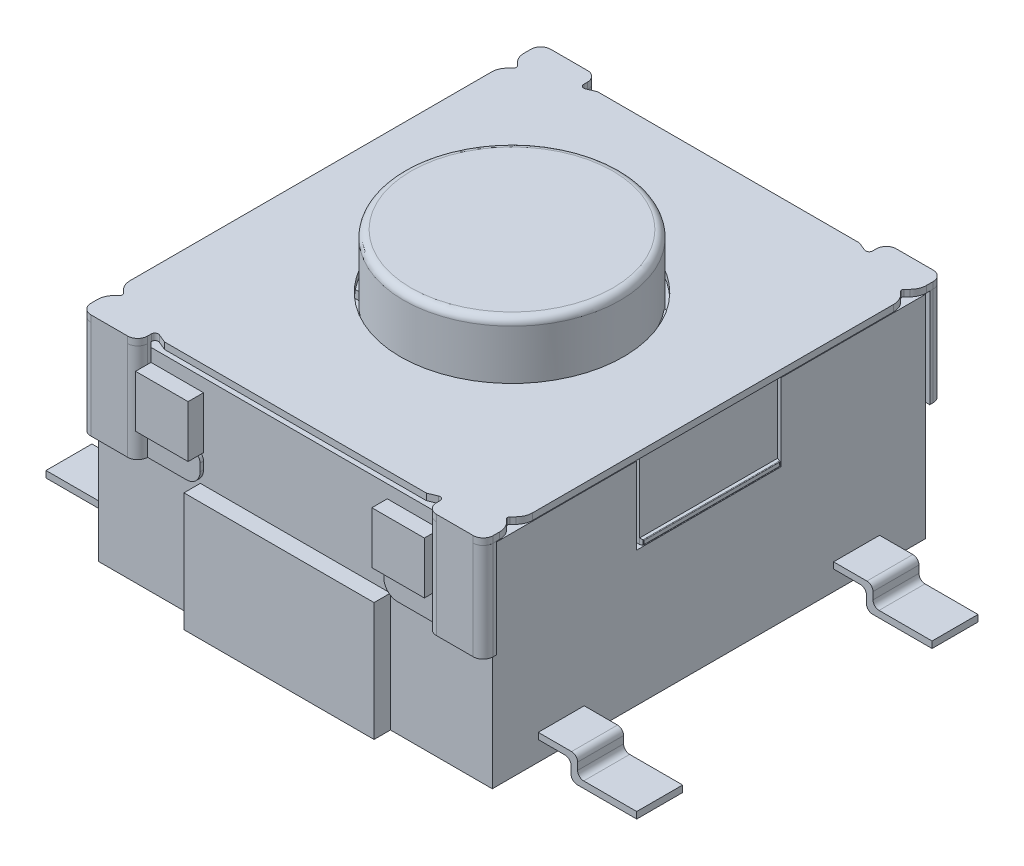
SolidWorks part; units mm, degrees
ref_plane "Alzado" through (0, 0, 0) normal (0, 0, 1) x (1, 0, 0)
ref_plane "Planta" through (0, 0, 0) normal (0, 1, 0) x (1, 0, 0)
ref_plane "Vista lateral" through (0, 0, 0) normal (1, 0, 0) x (0, 0, -1)
sketch "Croquis1" plane through (0, 0, 0) normal (0, 0, 1) x (1, 0, 0)
  line L0 (0, 0) -> (9, 0) construction
  line L1 (4.5, 0) -> (4.5, 3.4) construction
  line L2 (4.5, 1.7) -> (7.5, 1.7) construction
  line L3 (4.5, 1.7) -> (1.5, 1.7) construction
  line L4 (1.5, 1.7) -> (1.5, 0) construction
  line L5 (7.5, 1.7) -> (7.5, 0) construction
  line L6 (1.5, 0.85) -> (1, 0.85) construction
  line L7 (7.5, 0.85) -> (8, 0.85) construction
  line L8 (0, 0) -> (0, 0.1) construction
  line L9 (0, 0) -> (0.9075, 0)
  line L10 (1, 0.0925) -> (1, 0.2069)
  line L11 (1.0925, 0.2994) -> (7.9075, 0.2994)
  line L13 (0, 0.1) -> (0, 0)
  line L14 (1, 0.2994) -> (0.9, 0.2994) construction
  line L15 (0.9, 0.2994) -> (0.9, 0.1925)
  line L16 (0.8075, 0.1) -> (0, 0.1)
  line L17 (8.0075, 0.3946) -> (0.9925, 0.3946)
  line L18 (0.9, 0.3021) -> (0.9, 0.2994)
  line L19 (8, 0.2994) -> (8.1, 0.2994) construction
  line L20 (9, 0) -> (9, 0.1) construction
  line L21 (7.5, 0.85) -> (8, 0.85) construction
  line L22 (8.1, 0.3021) -> (8.1, 0.2994)
  line L23 (8.1925, 0.1) -> (9, 0.1)
  line L24 (8.1, 0.2994) -> (8.1, 0.1925)
  line L25 (9, 0.1) -> (9, 0)
  line L26 (8, 0.0925) -> (8, 0.2069)
  line L27 (9, 0) -> (8.0925, 0)
  arc A0 (0.9, 0.3021) -> (0.9925, 0.3946) centre (0.9925, 0.3021) cw
  arc A1 (1, 0.2069) -> (1.0925, 0.2994) centre (1.0925, 0.2069) cw
  arc A2 (0.8075, 0.1) -> (0.9, 0.1925) centre (0.8075, 0.1925) ccw
  arc A3 (0.9075, 0) -> (1, 0.0925) centre (0.9075, 0.0925) ccw
  arc A4 (8.0925, 0) -> (8, 0.0925) centre (8.0925, 0.0925) cw
  arc A5 (8.1925, 0.1) -> (8.1, 0.1925) centre (8.1925, 0.1925) cw
  arc A6 (8, 0.2069) -> (7.9075, 0.2994) centre (7.9075, 0.2069) ccw
  arc A7 (8.1, 0.3021) -> (8.0075, 0.3946) centre (8.0075, 0.3021) ccw
  point P31 (1, 0)
  point P47 (8, 0)
  dimension "D9" = 0.0925
  dimension "D1" = 9
  dimension "D2" = 3
  dimension "D3" = 3
  dimension "D4" = 0.5
  dimension "D5" = 0.5
  dimension "D6" = 0.1
  dimension "D7" = 3.4
  dimension "D8" = 0.1
extrude "Saliente-Extruir1" add sketch "Croquis1" along normal blind 5.2
sketch "Croquis2" plane through (0, 0.3946, 0) normal (0, 1, 0) x (1, 0, 0)
  line L0 (4.5, 0) -> (4.5, -5.2) construction
  line L1 (8.0075, 0) -> (0.9925, 0) construction
  line L2 (8.0075, -5.2) -> (0.9925, -5.2) construction
  line L3 (0.9925, -2.6) -> (8.0075, -2.6) construction
  line L4 (0.9925, -5.2) -> (0.9925, 0) construction
  line L5 (8.0075, -5.2) -> (8.0075, 0) construction
  line L6 (9, -5.2) -> (9, 0) construction
  line L7 (0, -0.7) -> (9, -0.7)
  line L8 (0, -0.7) -> (0, -4.5)
  line L9 (0, -4.5) -> (9, -4.5)
  line L10 (9, -0.7) -> (9, -4.5)
  line L11 (0, -0.7) -> (9, -4.5) construction
  line L12 (0, -4.5) -> (9, -0.7) construction
  point P12 (4.5, -2.6)
  dimension "D1" = 3.8
extrude "Cortar-Extruir1" cut sketch "Croquis2" against normal blind 5.2
sketch "Croquis3" plane through (0, 0.2994, 0) normal (0, -1, 0) x (1, 0, 0)
  line L0 (4.5, 0.7) -> (4.5, 4.5) construction
  line L1 (7.9075, 0.7) -> (1.0925, 0.7) construction
  line L2 (1.0925, 4.5) -> (7.9075, 4.5) construction
  line L3 (3.7616, 2.6) -> (5.3308, 2.6) construction
  line L5 (7.5, -0.7) -> (1.5, -0.7)
  line L6 (7.5, -0.7) -> (7.5, 5.9)
  line L7 (7.5, 5.9) -> (1.5, 5.9)
  line L8 (1.5, -0.7) -> (1.5, 5.9)
  line L9 (7.5, -0.7) -> (1.5, 5.9) construction
  line L10 (7.5, 5.9) -> (1.5, -0.7) construction
  point P8 (4.5, 2.6)
  dimension "D1" = 6.6
  dimension "D2" = 6
extrude "Saliente-Extruir2" add sketch "Croquis3" along normal blind 0.3 and the other way blind 3
sketch "Croquis4" plane through (0, 3.2994, 0) normal (0, 1, 0) x (1, 0, 0)
  line L0 (4.5, 0.7) -> (4.5, -5.9) construction
  line L1 (1.5, 0.7) -> (7.5, 0.7) construction
  line L2 (7.5, -5.9) -> (1.5, -5.9) construction
  line L3 (4.5, -5.9) -> (1.5, -2.6) construction
  line L4 (1.5, -5.9) -> (1.5, 0.7) construction
  line L5 (1.5, -2.6) -> (7.5, -2.6) construction
  line L6 (7.5, 0.7) -> (7.5, -5.9) construction
  circle A0 centre (4.5, -2.6) radius 1.65
  dimension "D1" = 3.3
extrude "Cortar-Extruir2" cut sketch "Croquis4" against normal blind 1.3
sketch "Croquis5" plane through (0, 3.2994, 0) normal (0, 1, 0) x (1, 0, 0)
  line L0 (1.5, -5.9) -> (1.5, -6.3533) construction
  line L1 (1.5, -6.3533) -> (2.3, -6.3533) construction
  line L2 (4.5, -5.9) -> (4.5, -4.25) construction
  line L3 (7.5, -5.9) -> (1.5, -5.9) construction
  line L5 (2.5047, -5.9) -> (2.3734, -5.8453)
  line L6 (2.3, -5.8943) -> (2.3, -5.951)
  line L7 (2.1477, -6.1033) -> (1.5874, -6.1033)
  line L8 (1.4351, -5.951) -> (1.4351, -5.8529)
  line L9 (1.5097, -5.6729) -> (1.5536, -5.629)
  line L10 (1.581, -5.6016) -> (1.3352, -5.6016) construction
  line L11 (1.5097, -5.5303) -> (1.5536, -5.5742)
  line L12 (1.4351, -5.3503) -> (1.4351, -3.1032)
  line L14 (7.419, -5.6016) -> (7.6648, -5.6016) construction
  line L15 (7.5, -6.3533) -> (6.7, -6.3533) construction
  line L16 (7.5, -5.9) -> (7.5, -6.3533) construction
  line L17 (7.5649, -5.3503) -> (7.5649, -3.1032)
  line L18 (7.4903, -5.5303) -> (7.4464, -5.5742)
  line L19 (7.4903, -5.6729) -> (7.4464, -5.629)
  line L20 (7.5649, -5.951) -> (7.5649, -5.8529)
  line L21 (6.8523, -6.1033) -> (7.4126, -6.1033)
  line L22 (6.7, -5.8943) -> (6.7, -5.951)
  line L23 (6.4953, -5.9) -> (6.6266, -5.8453)
  line L24 (4.5, -2.6) -> (0.57, -2.6) construction
  line L25 (7.5, 0.7) -> (7.5, 1.1533) construction
  line L26 (7.5, 1.1533) -> (6.7, 1.1533) construction
  line L27 (7.419, 0.4016) -> (7.6648, 0.4016) construction
  line L28 (1.581, 0.4016) -> (1.3352, 0.4016) construction
  line L29 (4.5, 0.7) -> (4.5, -0.95) construction
  line L30 (1.5, 1.1533) -> (2.3, 1.1533) construction
  line L31 (1.5, 0.7) -> (1.5, 1.1533) construction
  line L32 (6.4953, 0.7) -> (6.6266, 0.6453)
  line L33 (6.7, 0.6943) -> (6.7, 0.751)
  line L34 (6.8523, 0.9033) -> (7.4126, 0.9033)
  line L35 (7.5649, 0.751) -> (7.5649, 0.6529)
  line L36 (7.4903, 0.4729) -> (7.4464, 0.429)
  line L37 (7.4903, 0.3303) -> (7.4464, 0.3742)
  line L38 (7.5649, 0.1503) -> (7.5649, -2.0968)
  line L40 (1.4351, 0.1503) -> (1.4351, -2.0968)
  line L41 (1.5097, 0.3303) -> (1.5536, 0.3742)
  line L42 (1.5097, 0.4729) -> (1.5536, 0.429)
  line L43 (1.4351, 0.751) -> (1.4351, 0.6529)
  line L44 (2.1477, 0.9033) -> (1.5874, 0.9033)
  line L45 (2.3, 0.6943) -> (2.3, 0.751)
  line L46 (2.5047, 0.7) -> (2.3734, 0.6453)
  line L48 (2.5047, 0.7) -> (6.4953, 0.7)
  line L49 (7.5649, -2.0968) -> (7.5649, -3.1032)
  line L50 (6.4953, -5.9) -> (2.5047, -5.9)
  line L51 (1.4351, -3.1032) -> (1.4351, -2.0968)
  circle A0 centre (4.5, -2.6) radius 1.65 construction
  arc A1 (1.5536, -5.629) -> (1.5536, -5.5742) centre (1.5262, -5.6016) ccw
  arc A2 (1.4351, -5.8529) -> (1.5097, -5.6729) centre (1.6897, -5.8529) cw
  arc A3 (1.5097, -5.5303) -> (1.4351, -5.3503) centre (1.6897, -5.3503) cw
  arc A4 (2.3, -5.951) -> (2.1477, -6.1033) centre (2.1477, -5.951) cw
  arc A5 (1.4351, -5.951) -> (1.5874, -6.1033) centre (1.5874, -5.951) ccw
  arc A6 (2.3734, -5.8453) -> (2.3, -5.8943) centre (2.353, -5.8943) ccw
  arc A7 (6.6266, -5.8453) -> (6.7, -5.8943) centre (6.647, -5.8943) cw
  arc A8 (7.5649, -5.951) -> (7.4126, -6.1033) centre (7.4126, -5.951) cw
  arc A9 (6.7, -5.951) -> (6.8523, -6.1033) centre (6.8523, -5.951) ccw
  arc A10 (7.4903, -5.5303) -> (7.5649, -5.3503) centre (7.3103, -5.3503) ccw
  arc A11 (7.5649, -5.8529) -> (7.4903, -5.6729) centre (7.3103, -5.8529) ccw
  arc A12 (7.4464, -5.629) -> (7.4464, -5.5742) centre (7.4738, -5.6016) cw
  arc A13 (7.4464, 0.429) -> (7.4464, 0.3742) centre (7.4738, 0.4016) ccw
  arc A14 (7.5649, 0.6529) -> (7.4903, 0.4729) centre (7.3103, 0.6529) cw
  arc A15 (7.4903, 0.3303) -> (7.5649, 0.1503) centre (7.3103, 0.1503) cw
  arc A16 (6.7, 0.751) -> (6.8523, 0.9033) centre (6.8523, 0.751) cw
  arc A17 (7.5649, 0.751) -> (7.4126, 0.9033) centre (7.4126, 0.751) ccw
  arc A18 (6.6266, 0.6453) -> (6.7, 0.6943) centre (6.647, 0.6943) ccw
  arc A19 (2.3734, 0.6453) -> (2.3, 0.6943) centre (2.353, 0.6943) cw
  arc A20 (1.4351, 0.751) -> (1.5874, 0.9033) centre (1.5874, 0.751) cw
  arc A21 (2.3, 0.751) -> (2.1477, 0.9033) centre (2.1477, 0.751) ccw
  arc A22 (1.5097, 0.3303) -> (1.4351, 0.1503) centre (1.6897, 0.1503) ccw
  arc A23 (1.4351, 0.6529) -> (1.5097, 0.4729) centre (1.6897, 0.6529) ccw
  arc A24 (1.5536, 0.429) -> (1.5536, 0.3742) centre (1.5262, 0.4016) cw
  point P26 (1.4351, -5.7475)
  point P29 (1.4351, -5.4558)
  point P61 (7.5649, -5.4558)
  point P62 (7.5649, -5.7475)
  point P118 (7.5649, 0.5475)
  point P119 (7.5649, 0.2558)
  point P120 (1.4351, 0.2558)
  point P121 (1.4351, 0.5475)
  dimension "D2" = 0.0387
  dimension "D3" = 0.2546
  dimension "D4" = 0.1523
  dimension "D5" = 0.053
  dimension "D1" = 0.8
extrude "Saliente-Extruir3" add sketch "Croquis5" along normal blind 0.1
sketch "Croquis6" plane through (0, 3.3994, 0) normal (0, 1, 0) x (1, 0, 0)
  line L0 (4.5, 0.7) -> (4.5, -5.9) construction
  line L1 (6.4953, 0.7) -> (2.5047, 0.7) construction
  line L2 (2.5047, -5.9) -> (6.4953, -5.9) construction
  line L3 (4.5, -5.9) -> (1.4351, -2.6) construction
  line L4 (1.4351, 0.1503) -> (1.4351, -5.3503) construction
  line L5 (1.4351, -2.6) -> (4.5, -2.6) construction
  circle A0 centre (4.5, -2.6) radius 1.7
  dimension "D1" = 3.4
extrude "Cortar-Extruir3" cut sketch "Croquis6" against normal blind 0.1
sketch "Croquis7" plane through (7.5, 0, 0) normal (1, 0, 0) x (0, 0, -1)
  line L0 (-2.6, 3.2994) -> (-2.6, 1.1616) construction
  line L1 (-5.3503, 3.2994) -> (0.1503, 3.2994) construction
  line L2 (-2.6, 1.1616) -> (-1.5, 1.1616) construction
  line L3 (-2.6, 1.1616) -> (-3.7, 1.1616) construction
  line L4 (-3.7, 1.1616) -> (-3.7, 3.2994) construction
  line L5 (-3.7, 3.2994) -> (-1.5, 1.1616) construction
  line L6 (-1.5, 1.1616) -> (-1.5, 3.2994) construction
  line L7 (0.3201, 3.2994) -> (-5.5201, 3.2994) construction
  line L8 (-5.2012, 3.2994) -> (-5.2012, 2.0494) construction
  line L9 (-5.2012, 2.0494) -> (0.7, 2.0494) construction
  line L10 (0.7, 3.2994) -> (0.7, -0.0006) construction
  line L11 (-5.9, 3.2994) -> (-3.6554, 3.2994)
  line L12 (0.7, 3.2242) -> (0.7, 3.2994)
  line L13 (0.7, 3.2242) -> (-1.5, 3.2242)
  line L14 (-1.5, 3.2242) -> (-1.5, 2.0494)
  line L15 (-1.5, 2.0494) -> (-3.7, 2.0494)
  line L16 (-3.7, 2.0494) -> (-3.7, 3.2242)
  line L17 (-3.7, 3.2242) -> (-5.9, 3.2242)
  line L18 (-5.9, 3.2994) -> (-5.9, -0.0006) construction
  line L19 (-5.9, 3.2242) -> (-5.9, 3.2994)
  line L21 (-3.6554, 3.2994) -> (-3.6554, 2.1002)
  line L22 (-3.6554, 2.1002) -> (-1.5557, 2.1002)
  line L23 (-1.5557, 2.1002) -> (-1.5557, 3.2994)
  line L24 (-1.5557, 3.2994) -> (0.7, 3.2994)
  dimension "D1" = 1.1
  dimension "D2" = 1.1
  dimension "D3" = 1.25
extrude "Cortar-Extruir4" cut sketch "Croquis7" against normal blind 7.1
sketch "Croquis9" plane through (7.5, 0, 0) normal (1, 0, 0) x (0, 0, -1)
  line L0 (-3.6554, 2.1002) -> (-3.6554, 3.2994) construction
  line L1 (-1.5557, 2.1002) -> (-3.6554, 2.1002)
  line L2 (-1.5557, 2.1002) -> (-1.5557, 2.1873)
  line L3 (-1.5557, 2.1873) -> (-3.6554, 2.1873)
  line L4 (-3.6554, 2.1002) -> (-3.6554, 2.1873)
extrude "Saliente-Extruir4" add sketch "Croquis9" along normal blind 0.05 draft 10
fillet "Redondeo1" radius 0.01 4 edges at (7.55, 2.109, 2.6055) (7.55, 2.1437, 3.6466) (7.55, 2.1785, 2.6055) (7.55, 2.1437, 1.5645)
sketch "Croquis10" plane through (1.5, 0, 0) normal (-1, 0, 0) x (0, 0, 1)
  line L0 (1.5557, 2.1002) -> (1.5557, 3.2994) construction
  line L1 (3.6554, 2.1002) -> (1.5557, 2.1002)
  line L2 (3.6554, 2.1002) -> (3.6554, 2.2063)
  line L3 (3.6554, 2.2063) -> (1.5557, 2.2063)
  line L4 (1.5557, 2.1002) -> (1.5557, 2.2063)
extrude "Saliente-Extruir5" add sketch "Croquis10" along normal blind 0.05 draft 10
fillet "Redondeo2" radius 0.01 4 edges at (1.45, 2.109, 2.6055) (1.45, 2.1532, 1.5645) (1.45, 2.1975, 2.6055) (1.45, 2.1532, 3.6466)
sketch "Croquis11" plane through (0, 3.2994, 0) normal (0, -1, 0) x (1, 0, 0)
  line L2 (2.1477, 6.1033) -> (2.3213, 6.1033) construction
  line L3 (2.3, 5.9) -> (2.3, 5.9512)
  line L4 (2.3, 5.951) -> (2.3, 5.8943) construction
  line L5 (7.5, 5.9) -> (1.5, 5.9) construction
  line L6 (2.1478, 6.1033) -> (2.1477, 6.1033)
  line L7 (1.5, 5.9) -> (1.3098, 5.9) construction
  line L8 (1.5, 5.9) -> (1.5, -0.7) construction
  line L9 (1.5874, 6.1033) -> (1.2856, 6.1033) construction
  line L10 (1.4346, 5.9) -> (1.4351, 5.9526)
  line L11 (1.5872, 6.1033) -> (1.5874, 6.1033)
  line L12 (1.5874, 6.1033) -> (2.1477, 6.1033)
  line L13 (1.4346, 5.9) -> (2.3, 5.9)
  line L14 (4.5, 5.9) -> (4.5, -0.7) construction
  line L15 (1.5, -0.7) -> (7.5, -0.7) construction
  line L16 (4.5, 2.6) -> (1.5, 2.6) construction
  line L17 (7.4126, 6.1033) -> (7.7144, 6.1033) construction
  line L18 (7.5, 5.9) -> (7.6902, 5.9) construction
  line L19 (6.8523, 6.1033) -> (6.6787, 6.1033) construction
  line L20 (7.5654, 5.9) -> (6.7, 5.9)
  line L21 (7.4126, 6.1033) -> (6.8523, 6.1033)
  line L22 (7.4128, 6.1033) -> (7.4126, 6.1033)
  line L23 (7.5654, 5.9) -> (7.5649, 5.9526)
  line L24 (6.8522, 6.1033) -> (6.8523, 6.1033)
  line L25 (6.7, 5.9) -> (6.7, 5.9512)
  line L26 (6.8523, -0.9033) -> (6.6787, -0.9033) construction
  line L27 (7.5, -0.7) -> (7.6902, -0.7) construction
  line L28 (7.4126, -0.9033) -> (7.7144, -0.9033) construction
  line L29 (1.5874, -0.9033) -> (1.2856, -0.9033) construction
  line L30 (1.5, -0.7) -> (1.3098, -0.7) construction
  line L31 (2.1477, -0.9033) -> (2.3213, -0.9033) construction
  line L32 (6.7, -0.7) -> (6.7, -0.7512)
  line L33 (6.8522, -0.9033) -> (6.8523, -0.9033)
  line L34 (7.5654, -0.7) -> (7.5649, -0.7526)
  line L35 (7.4128, -0.9033) -> (7.4126, -0.9033)
  line L36 (7.4126, -0.9033) -> (6.8523, -0.9033)
  line L37 (7.5654, -0.7) -> (6.7, -0.7)
  line L38 (1.4346, -0.7) -> (2.3, -0.7)
  line L39 (1.5874, -0.9033) -> (2.1477, -0.9033)
  line L40 (1.5872, -0.9033) -> (1.5874, -0.9033)
  line L41 (1.4346, -0.7) -> (1.4351, -0.7526)
  line L42 (2.1478, -0.9033) -> (2.1477, -0.9033)
  line L43 (2.3, -0.7) -> (2.3, -0.7512)
  arc A1 (2.3, 5.9512) -> (2.1478, 6.1033) centre (2.1478, 5.9512) ccw
  arc A2 (1.4351, 5.9526) -> (1.5872, 6.1033) centre (1.5872, 5.9512) cw
  arc A3 (7.5649, 5.9526) -> (7.4128, 6.1033) centre (7.4128, 5.9512) ccw
  arc A4 (6.7, 5.9512) -> (6.8522, 6.1033) centre (6.8522, 5.9512) cw
  arc A5 (6.7, -0.7512) -> (6.8522, -0.9033) centre (6.8522, -0.7512) ccw
  arc A6 (7.5649, -0.7526) -> (7.4128, -0.9033) centre (7.4128, -0.7512) cw
  arc A7 (1.4351, -0.7526) -> (1.5872, -0.9033) centre (1.5872, -0.7512) ccw
  arc A8 (2.3, -0.7512) -> (2.1478, -0.9033) centre (2.1478, -0.7512) cw
  point P10 (2.3, 6.1033)
  point P23 (1.4365, 6.1033)
  point P44 (7.5635, 6.1033)
  point P45 (6.7, 6.1033)
  point P74 (6.7, -0.9033)
  point P75 (7.5635, -0.9033)
  point P76 (1.4365, -0.9033)
  point P77 (2.3, -0.9033)
  dimension "D1" = 0.1522
  dimension "D2" = 0.1522
extrude "Saliente-Extruir6" add sketch "Croquis11" along normal blind 1.5
sketch "Croquis12" plane through (2.3, 0, 0) normal (1, 0, 0) x (0, 0, -1)
  line L0 (-5.9526, 1.7994) -> (-5.9526, 3.2994) construction
  line L1 (-5.9, 1.7994) -> (-5.9526, 1.7994)
  line L2 (-5.9, 1.7994) -> (-5.9, 2.2341)
  line L3 (-5.9, 2.2341) -> (-5.9526, 2.2341)
  line L4 (-5.9526, 1.7994) -> (-5.9526, 2.2341)
extrude "Saliente-Extruir7" add sketch "Croquis12" along normal blind 0.8
fillet "Redondeo4" radius 0.21 1 edges at (3.1, 1.7994, 5.9263)
fillet "Redondeo5" radius 0.11 1 edges at (3.1, 2.2341, 5.9263)
sketch "Croquis13" plane through (6.7, 0, 0) normal (-1, 0, 0) x (0, 0, 1)
  line L0 (5.9, 3.2242) -> (5.9, 1.7994) construction
  line L1 (5.9526, 1.7994) -> (5.9, 1.7994)
  line L2 (5.9526, 1.7994) -> (5.9526, 2.2282)
  line L3 (5.9526, 2.2282) -> (5.9, 2.2282)
  line L4 (5.9, 1.7994) -> (5.9, 2.2282)
extrude "Saliente-Extruir8" add sketch "Croquis13" along normal blind 0.8
fillet "Redondeo6" radius 0.21 1 edges at (5.9, 1.7994, 5.9263)
fillet "Redondeo7" radius 0.11 1 edges at (5.9, 2.2282, 5.9263)
sketch "Croquis14" plane through (6.7, 0, 0) normal (-1, 0, 0) x (0, 0, 1)
  line L0 (-0.7526, 1.7994) -> (-0.7526, 3.2994) construction
  line L1 (-0.7, 1.7994) -> (-0.7526, 1.7994)
  line L2 (-0.7, 1.7994) -> (-0.7, 2.2283)
  line L3 (-0.7, 2.2283) -> (-0.7526, 2.2283)
  line L4 (-0.7526, 1.7994) -> (-0.7526, 2.2283)
extrude "Saliente-Extruir9" add sketch "Croquis14" along normal blind 0.8
fillet "Redondeo8" radius 0.21 1 edges at (5.9, 1.7994, -0.7263)
fillet "Redondeo9" radius 0.11 1 edges at (5.9, 2.2283, -0.7263)
sketch "Croquis15" plane through (2.3, 0, 0) normal (1, 0, 0) x (0, 0, -1)
  line L0 (0.7, 3.2242) -> (0.7, 1.7994) construction
  line L1 (0.7512, 1.7994) -> (0.7, 1.7994)
  line L2 (0.7512, 1.7994) -> (0.7512, 2.2355)
  line L3 (0.7512, 2.2355) -> (0.7, 2.2355)
  line L4 (0.7, 1.7994) -> (0.7, 2.2355)
extrude "Saliente-Extruir10" add sketch "Croquis15" along normal blind 0.8
fillet "Redondeo10" radius 0.11 1 edges at (3.1, 2.2355, -0.7256)
fillet "Redondeo11" radius 0.21 1 edges at (3.1, 1.7994, -0.7256)
sketch "Croquis16" plane through (0, 0, -0.7) normal (0, 0, -1) x (-1, 0, 0)
  line L0 (-6.7, 2.2348) -> (-5.6092, 2.2348) construction
  line L1 (-6.7, 2.2283) -> (-6.7, 3.2242) construction
  line L2 (-5.9, 2.0094) -> (-5.9, 2.5471) construction
  line L3 (-4.5, 3.2242) -> (-4.5, 2.0094) construction
  line L4 (-5.9, 2.2348) -> (-6.7, 2.2348)
  line L5 (-5.9, 2.2348) -> (-5.9, 3.0259)
  line L6 (-5.9, 3.0259) -> (-6.7, 3.0259)
  line L7 (-6.7, 2.2348) -> (-6.7, 3.0259)
  line L8 (-2.3, 3.2242) -> (-6.7, 3.2242) construction
  line L9 (-3.1, 2.0094) -> (-3.1, 2.5471) construction
  line L10 (-2.3, 2.2348) -> (-3.3908, 2.2348) construction
  line L11 (-2.3, 2.2348) -> (-2.3, 3.0259)
  line L12 (-3.1, 3.0259) -> (-2.3, 3.0259)
  line L13 (-3.1, 2.2348) -> (-3.1, 3.0259)
  line L14 (-3.1, 2.2348) -> (-2.3, 2.2348)
extrude "Saliente-Extruir11" add sketch "Croquis16" along normal blind 0.23 and the other way blind 6.835
sketch "Croquis17" plane through (0, 0, -0.7) normal (0, 0, -1) x (-1, 0, 0)
  line L0 (-4.5, -0.0006) -> (-4.5, 3.2242) construction
  line L1 (-1.5, -0.0006) -> (-7.5, -0.0006) construction
  line L2 (-2.3, 3.2242) -> (-6.7, 3.2242) construction
  line L3 (-6.1155, 1.7994) -> (-2.8111, 1.7994) construction
  line L4 (-7.5, 1.7994) -> (-6.11, 1.7994) construction
  line L5 (-2.89, 1.7994) -> (-1.5, 1.7994) construction
  line L6 (-4.5, -0.0006) -> (-4.5, 0.9026) construction
  line L7 (-4.5, 0.9026) -> (-5.6406, 0.9026) construction
  line L9 (-3.0518, 1.8059) -> (-5.9482, 1.8059)
  line L10 (-3.0518, 1.8059) -> (-3.0518, -0.0006)
  line L11 (-3.0518, -0.0006) -> (-5.9482, -0.0006)
  line L12 (-5.9482, 1.8059) -> (-5.9482, -0.0006)
  line L13 (-3.0518, 1.8059) -> (-5.9482, -0.0006) construction
  line L14 (-3.0518, -0.0006) -> (-5.9482, 1.8059) construction
extrude "Saliente-Extruir12" add sketch "Croquis17" along normal blind 0.23 and the other way blind 6.85
sketch "Croquis18" plane through (0, 1.9994, 0) normal (0, 1, 0) x (1, 0, 0)
  line L0 (4.5, -0.95) -> (4.5, -4.25) construction
  line L1 (4.5, -4.25) -> (6.2, -2.6) construction
  line L2 (6.2, -2.6) -> (4.5, -2.6) construction
  arc A0 (5.7298, -1.5) -> (3.2702, -1.5) centre (4.5, -2.6) ccw construction
  arc A1 (3.2702, -3.7) -> (5.7298, -3.7) centre (4.5, -2.6) ccw construction
  circle A2 centre (4.5, -2.6) radius 1.7 construction
  circle A3 centre (4.5, -2.6) radius 1.65
extrude "Cortar-Extruir5" cut sketch "Croquis18" along normal blind 2.23
sketch "Croquis19" plane through (0, 1.9994, 0) normal (0, 1, 0) x (1, 0, 0)
  line L0 (2.8, -2.6071) -> (4.5, -2.6) construction
  line L1 (4.5, -2.6) -> (4.5, -0.95) construction
  arc A0 (3.1586, -1.5557) -> (3.1673, -3.6554) centre (4.5, -2.6) ccw construction
  arc A1 (5.7298, -1.5) -> (3.2702, -1.5) centre (4.5, -2.6) ccw construction
  circle A2 centre (4.5, -2.6) radius 1.65
extrude "Saliente-Extruir13" add sketch "Croquis19" along normal blind 2.23
fillet "Redondeo12" radius 0.11 1 edges at (4.5, 4.2294, 4.25)
